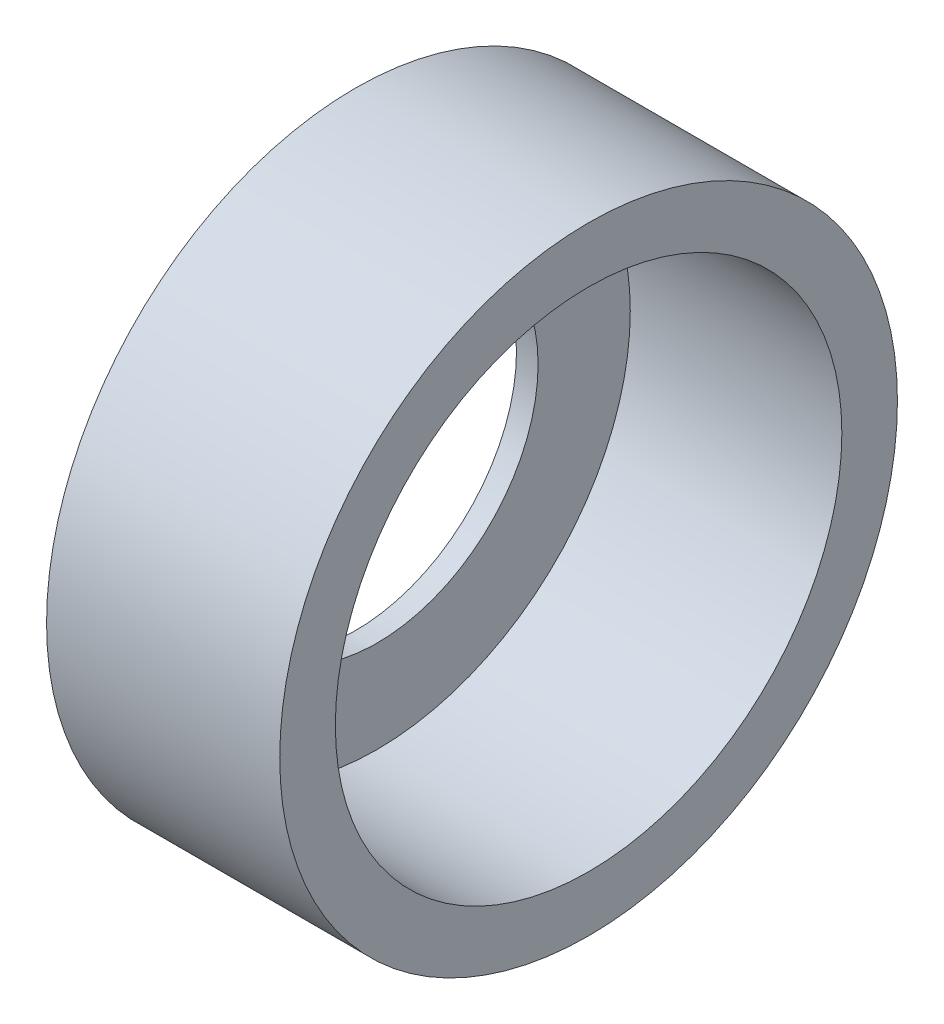
SolidWorks part; units mm, degrees
ref_plane "Ebene vorne" through (0, 0, 0) normal (0, 0, 1) x (1, 0, 0)
ref_plane "Ebene oben" through (0, 0, 0) normal (0, 1, 0) x (1, 0, 0)
ref_plane "Ebene rechts" through (0, 0, 0) normal (1, 0, 0) x (0, 0, -1)
sketch "Skizze2" plane through (0, 0, 0) normal (0, 0, 1) x (1, 0, 0)
  line L0 (0, 0) -> (-33680.1149, 0) construction
  line L1 (0, 26.075) -> (3.5, 26.075)
  line L2 (3.5, 26.075) -> (3.5, 41)
  line L3 (3.5, 41) -> (37.75, 41)
  line L4 (37.75, 41) -> (37.75, 50)
  line L5 (37.75, 50) -> (0, 50)
  line L6 (0, 50) -> (0, 26.075)
  line L7 (0, 0) -> (0, 50000) construction
  dimension "D1" = 52.15
  dimension "D2" = 3.5
  dimension "D3" = 37.75
  dimension "D4" = 100
  dimension "D5" = 82
revolve "Rotation1" add sketch "Skizze2" angle 360 about L0
sketch "Skizze4" plane through (37.75, 0, 0) normal (1, 0, 0) x (0, 0, -1)
  line L0 (0, 0) -> (-50000, 0) construction
  line L1 (0, 0) -> (38.2229, -11.7902) construction
  line L2 (0, 0) -> (57.0555, -17.5993) construction
  arc A0 (40.3511, -7.2657) -> (40.7, -4.9508) centre (0, 0) ccw
  circle A1 centre (0, 0) radius 40 construction
  arc A2 (40.7, -4.9508) -> (45, 0) centre (40, 0) ccw
  arc A3 (43.0008, -13.264) -> (40.3511, -7.2657) centre (38.2229, -11.7902) ccw
  arc A4 (37.4326, -16.7273) -> (43.0008, -13.264) centre (38.2229, -11.7902) ccw
  arc A5 (36.4168, -18.8366) -> (37.4326, -16.7273) centre (0, 0) ccw
  arc A6 (37.1807, -25.3494) -> (36.4168, -18.8366) centre (33.0496, -22.5328) ccw
  arc A7 (30.8391, -27.0176) -> (37.1807, -25.3494) centre (33.0496, -22.5328) ccw
  arc A8 (29.2467, -28.7338) -> (30.8391, -27.0176) centre (0, 0) ccw
  arc A9 (28.057, -35.1824) -> (29.2467, -28.7338) centre (24.9396, -31.2733) ccw
  arc A10 (21.5054, -34.9073) -> (28.057, -35.1824) centre (24.9396, -31.2733) ccw
  arc A11 (19.4779, -36.0778) -> (21.5054, -34.9073) centre (0, 0) ccw
  arc A12 (16.4403, -41.8893) -> (19.4779, -36.0778) centre (14.6136, -37.2349) ccw
  arc A13 (10.2608, -39.6953) -> (16.4403, -41.8893) centre (14.6136, -37.2349) ccw
  arc A14 (7.9784, -40.2162) -> (10.2608, -39.6953) centre (0, 0) ccw
  arc A15 (3.3629, -44.8742) -> (7.9784, -40.2162) centre (2.9892, -39.8882) ccw
  arc A16 (-1.8954, -40.9562) -> (3.3629, -44.8742) centre (2.9892, -39.8882) ccw
  arc A17 (-4.23, -40.7812) -> (-1.8954, -40.9562) centre (0, 0) ccw
  arc A18 (-10.0134, -43.8718) -> (-4.23, -40.7812) centre (-8.9008, -38.9971) ccw
  arc A19 (-13.8832, -38.5779) -> (-10.0134, -43.8718) centre (-8.9008, -38.9971) ccw
  arc A20 (-16.0625, -37.7226) -> (-13.8832, -38.5779) centre (0, 0) ccw
  arc A21 (-22.5, -38.9711) -> (-16.0625, -37.7226) centre (-20, -34.641) ccw
  arc A22 (-24.6375, -32.7719) -> (-22.5, -38.9711) centre (-20, -34.641) ccw
  arc A23 (-26.4678, -31.3122) -> (-24.6375, -32.7719) centre (0, 0) ccw
  arc A24 (-32.9873, -30.6078) -> (-26.4678, -31.3122) centre (-29.3221, -27.2069) ccw
  arc A25 (-33.2026, -24.0539) -> (-32.9873, -30.6078) centre (-29.3221, -27.2069) ccw
  arc A26 (-34.5214, -22.1195) -> (-33.2026, -24.0539) centre (0, 0) ccw
  arc A27 (-40.5436, -19.5248) -> (-34.5214, -22.1195) centre (-36.0388, -17.3553) ccw
  arc A28 (-38.8175, -13.1986) -> (-40.5436, -19.5248) centre (-36.0388, -17.3553) ccw
  arc A29 (-39.5075, -10.9615) -> (-38.8175, -13.1986) centre (0, 0) ccw
  arc A30 (-44.4974, -6.7069) -> (-39.5075, -10.9615) centre (-39.5532, -5.9617) ccw
  arc A31 (-40.9833, -1.1706) -> (-44.4974, -6.7069) centre (-39.5532, -5.9617) ccw
  arc A32 (-40.9833, 1.1706) -> (-40.9833, -1.1706) centre (0, 0) ccw
  arc A33 (-44.4974, 6.7069) -> (-40.9833, 1.1706) centre (-39.5532, 5.9617) ccw
  arc A34 (-39.5075, 10.9615) -> (-44.4974, 6.7069) centre (-39.5532, 5.9617) ccw
  arc A35 (-38.8175, 13.1986) -> (-39.5075, 10.9615) centre (0, 0) ccw
  arc A36 (-40.5436, 19.5248) -> (-38.8175, 13.1986) centre (-36.0388, 17.3553) ccw
  arc A37 (-34.5214, 22.1195) -> (-40.5436, 19.5248) centre (-36.0388, 17.3553) ccw
  arc A38 (-33.2026, 24.0539) -> (-34.5214, 22.1195) centre (0, 0) ccw
  arc A39 (-32.9873, 30.6078) -> (-33.2026, 24.0539) centre (-29.3221, 27.2069) ccw
  arc A40 (-26.4678, 31.3122) -> (-32.9873, 30.6078) centre (-29.3221, 27.2069) ccw
  arc A41 (-24.6375, 32.7719) -> (-26.4678, 31.3122) centre (0, 0) ccw
  arc A42 (-22.5, 38.9711) -> (-24.6375, 32.7719) centre (-20, 34.641) ccw
  arc A43 (-16.0625, 37.7226) -> (-22.5, 38.9711) centre (-20, 34.641) ccw
  arc A44 (-13.8832, 38.5779) -> (-16.0625, 37.7226) centre (0, 0) ccw
  arc A45 (-10.0134, 43.8718) -> (-13.8832, 38.5779) centre (-8.9008, 38.9971) ccw
  arc A46 (-4.23, 40.7812) -> (-10.0134, 43.8718) centre (-8.9008, 38.9971) ccw
  arc A47 (-1.8954, 40.9562) -> (-4.23, 40.7812) centre (0, 0) ccw
  arc A48 (3.3629, 44.8742) -> (-1.8954, 40.9562) centre (2.9892, 39.8882) ccw
  arc A49 (7.9784, 40.2162) -> (3.3629, 44.8742) centre (2.9892, 39.8882) ccw
  arc A50 (10.2608, 39.6953) -> (7.9784, 40.2162) centre (0, 0) ccw
  arc A51 (16.4403, 41.8893) -> (10.2608, 39.6953) centre (14.6136, 37.2349) ccw
  arc A52 (19.4779, 36.0778) -> (16.4403, 41.8893) centre (14.6136, 37.2349) ccw
  arc A53 (21.5054, 34.9073) -> (19.4779, 36.0778) centre (0, 0) ccw
  arc A54 (28.057, 35.1824) -> (21.5054, 34.9073) centre (24.9396, 31.2733) ccw
  arc A55 (29.2467, 28.7338) -> (28.057, 35.1824) centre (24.9396, 31.2733) ccw
  arc A56 (30.8391, 27.0176) -> (29.2467, 28.7338) centre (0, 0) ccw
  arc A57 (37.1807, 25.3494) -> (30.8391, 27.0176) centre (33.0496, 22.5328) ccw
  arc A58 (36.4168, 18.8366) -> (37.1807, 25.3494) centre (33.0496, 22.5328) ccw
  arc A59 (37.4326, 16.7273) -> (36.4168, 18.8366) centre (0, 0) ccw
  arc A60 (43.0008, 13.264) -> (37.4326, 16.7273) centre (38.2229, 11.7902) ccw
  arc A61 (40.3511, 7.2657) -> (43.0008, 13.264) centre (38.2229, 11.7902) ccw
  arc A62 (40.7, 4.9508) -> (40.3511, 7.2657) centre (0, 0) ccw
  arc A63 (45, 0) -> (40.7, 4.9508) centre (40, 0) ccw
  circle A65 centre (0, 0) radius 50
  point P135 (0, 0)
  dimension "D1" = 82
  dimension "D2" = 80
  dimension "D3" = 10
  dimension "D6" = 100
  dimension "D4" = 17.143
  dimension "D5" = 21
